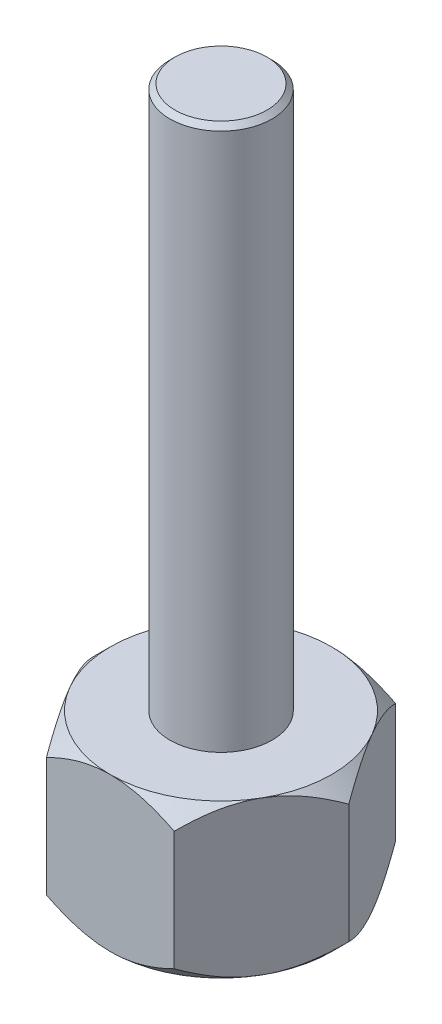
SolidWorks part; units mm, degrees
material "Plain Carbon Steel"
ref_plane "Front Plane" through (0, 0, 0) normal (0, 0, 1) x (1, 0, 0)
ref_plane "Top Plane" through (0, 0, 0) normal (0, 1, 0) x (1, 0, 0)
ref_plane "Right Plane" through (0, 0, 0) normal (1, 0, 0) x (0, 0, -1)
sketch "Sketch1" plane through (0, 0, 0) normal (0, 1, 0) x (1, 0, 0)
  line L1 (-2.5, -4.3301) -> (2.5, -4.3301)
  line L2 (2.5, -4.3301) -> (5, 0)
  line L3 (5, 0) -> (2.5, 4.3301)
  line L4 (2.5, 4.3301) -> (-2.5, 4.3301)
  line L5 (-2.5, 4.3301) -> (-5, 0)
  line L6 (-5, 0) -> (-2.5, -4.3301)
  circle A0 centre (0, 0) radius 4.3301 construction
  circle A1 centre (0, 0) radius 2
  dimension "D2" = 4
  dimension "D1" = 10
extrude "Boss-Extrude1" add sketch "Sketch1" along normal blind 6 contours L1 L2 L3 L4 L5 L6
extrude "Boss-Extrude2" add sketch "Sketch1<3>" along normal blind 27.25 contours A1
sketch "Sketch1<3>" plane through (0, 0, 0) normal (0, 1, 0) x (1, 0, 0) same geometry as "Sketch1"
sketch "Sketch2" plane through (0, 0, 0) normal (0, -1, 0) x (1, 0, 0)
  line L0 (-5, 0) -> (-2.5, 4.3301) construction
  circle A0 centre (0, 0) radius 4.3301
extrude "Cut-Extrude5" cut sketch "Sketch2" against normal through all draft 45 flip side to cut
chamfer "Chamfer1" distance 0.2 angle 45 1 edges at (0, 27.25, 2)
sketch "Sketch3" plane through (0, 6, 0) normal (0, 1, 0) x (1, 0, 0)
  line L0 (-2.5, 4.3301) -> (-5, 0) construction
  circle A0 centre (0, 0) radius 4.3301
extrude "Cut-Extrude6" cut sketch "Sketch3" against normal through all draft 45 flip side to cut
